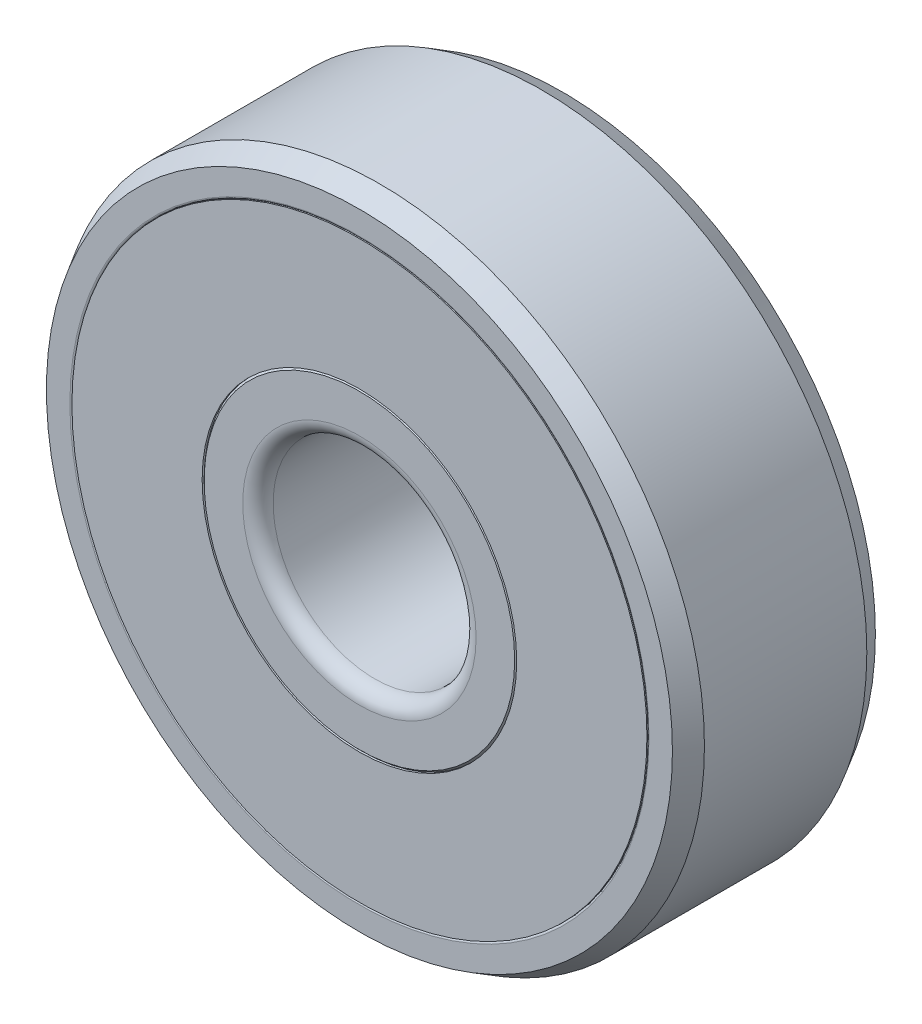
SolidWorks part; units mm, degrees
ref_plane "Front Plane" through (0, 0, 0) normal (0, 0, 1) x (1, 0, 0)
ref_plane "Top Plane" through (0, 0, 0) normal (0, 1, 0) x (1, 0, 0)
ref_plane "Right Plane" through (0, 0, 0) normal (1, 0, 0) x (0, 0, -1)
sketch "Sketch1" plane through (0, 0, 0) normal (0, 0, 1) x (1, 0, 0)
  line L0 (0, 5.25) -> (0, 8) construction
  line L1 (0, 2.5) -> (0, 5.25) construction
  line L2 (0, 8) -> (0, 7.0833) construction
  line L3 (0, 7.0833) -> (0, 6.1667) construction
  line L4 (0, 6.1667) -> (0, 5.25) construction
  circle A0 centre (0, 0) radius 2.5
  circle A1 centre (0, 0) radius 8
  circle A2 centre (0, 0) radius 7.0833 construction
  circle A4 centre (0, 0) radius 3.875 construction
  point P6 (0, 3.875)
  dimension "OD" = 16
  dimension "ID" = 5
sketch "Sketch2" plane through (0, 0, 0) normal (1, 0, 0) x (0, 0, -1)
  line L0 (-2.5, 8) -> (2.5, 8) construction
  line L1 (2.5, 8) -> (2.5, -8) construction
  line L2 (2.5, 0) -> (-2.5, 0) construction
  line L3 (-2.5, 2.5) -> (-2.5, -2.5) construction
  point P2 (0, 8)
  dimension "Width" = 5
  dimension "For Shaft Diameter" = 5
  dimension "For Housing ID" = 16
sketch "Sketch3" plane through (0, 0, 0) normal (1, 0, 0) x (0, 0, -1)
  line L0 (-2, -8) -> (2, -8)
  line L3 (-2.5, -7.1333) -> (-2.5, -7.7113)
  line L4 (0, -3.875) -> (0, -7.0833) construction
  line L5 (-2, -8) -> (-2.5, -7.7113)
  line L6 (-2.125, -2.5) -> (2.125, -2.5)
  line L7 (-1.5278, -7.0833) -> (-1.5278, -7.3889) construction
  line L8 (-2.45, -3.875) -> (-1.5278, -3.875)
  line L9 (-2.5, -3.875) -> (0, -3.875) construction
  line L11 (-2.5, -7.0833) -> (-2.5, -3.875) construction
  line L12 (-2.5, -3.825) -> (-2.5, -2.875)
  line L14 (-2.5, 0) -> (2.5, 0) construction
  line L15 (-2.45, -7.0833) -> (-1.5278, -7.0833)
  line L17 (0, 0) -> (0, -8) construction
  line L18 (-1.5278, -7.3889) -> (-1.5278, -7.6944) construction
  line L19 (2, -8) -> (2.5, -7.7113)
  line L20 (0, -7.0833) -> (-2.5, -7.0833) construction
  line L21 (-2.5, 2.5) -> (-2.5, -2.5) construction
  line L22 (-1.5278, -7.6944) -> (-1.5278, -8) construction
  line L30 (-2.5, -3.825) -> (-2.45, -3.875)
  line L31 (2.45, -3.875) -> (1.5278, -3.875)
  line L32 (2.5, -3.825) -> (2.45, -3.875)
  line L33 (2.5, -3.825) -> (2.5, -2.875)
  line L34 (2.45, -7.0833) -> (1.5278, -7.0833)
  line L35 (2.5, -7.1333) -> (2.5, -7.7113)
  line L36 (0, 8) -> (0, -8) construction
  arc A0 (0, -3.2639) -> (0, -7.6944) centre (0, -5.4792) ccw construction
  arc A1 (-1.5278, -3.875) -> (1.5278, -3.875) centre (0, -5.4792) cw
  arc A2 (-1.5278, -7.0833) -> (1.5278, -7.0833) centre (0, -5.4792) ccw
  arc A4 (-2.45, -7.0833) -> (-2.5, -7.1333) centre (-2.45, -7.1333) ccw
  arc A5 (-2.125, -2.5) -> (-2.5, -2.875) centre (-2.125, -2.875) ccw
  arc A6 (2.125, -2.5) -> (2.5, -2.875) centre (2.125, -2.875) cw
  arc A7 (2.45, -7.0833) -> (2.5, -7.1333) centre (2.45, -7.1333) cw
  point P28 (0, -5.4792)
  point P46 (-2.5, -2.5)
  point P54 (0, -2.5)
  dimension "D4" = 0.05
  dimension "D7" = 0.375
  dimension "D5" = 45
  dimension "D6" = 0.05
  dimension "D3" = 0.5
  dimension "D2" = 60
revolve "Revolve1" add sketch "Sketch3" angle 360 about L14
sketch "Sketch4" plane through (0, 0, 0) normal (1, 0, 0) x (0, 0, -1)
  line L0 (-2.45, -7.0833) -> (-1.5278, -7.0833) construction
  line L1 (-2.5, -3.875) -> (-2.2865, -3.875)
  line L2 (-2.5, -3.875) -> (-2.5, -7.0833)
  line L3 (-2.5, -7.0833) -> (-2.2865, -7.0833)
  line L4 (-2.2865, -3.875) -> (-2.2865, -7.0833)
  line L5 (-2.5, -3.825) -> (-2.5, -2.875) construction
  line L6 (-2.5, -5.4792) -> (-2.4288, -5.4792) construction
  line L7 (-2.4288, -5.4792) -> (-2.3576, -5.4792) construction
  line L8 (-2.3576, -5.4792) -> (-2.2865, -5.4792) construction
  line L9 (-2.2865, -5.4792) -> (-2.2153, -5.4792) construction
  line L10 (-2.5, -7.0833) -> (-2.5, -3.875) construction
  line L11 (-2.45, -3.875) -> (-1.5278, -3.875) construction
  arc A1 (0, -3.2639) -> (0, -7.6944) centre (0, -5.4792) ccw construction
revolve "Revolve2" add sketch "Sketch4" angle 360 about L14
sketch "Sketch5" plane through (0, 0, 0) normal (1, 0, 0) x (0, 0, -1)
  line L2 (0, -3.2639) -> (0, -7.6944)
  arc A2 (0, -7.6944) -> (0, -3.2639) centre (0, -5.4792) cw
revolve "Revolve3" add sketch "Sketch5" angle 360 about L17
pattern_circular "CirPattern1" count 7 over 360 about axis through (0, 0, 2.5) along (0, 0, -1) of bodies 138
ref_axis "Bearing Axis" through (0, 0, -13.2133) along (0, 0, 1)
equation "\"D4@Sketch3\"=\"Width@Sketch2\"*.01"
equation "\"D6@Sketch3\"=\"Width@Sketch2\"*.01"
equation "\"D7@Sketch3\"=\"Width@Sketch2\"*.075"
equation "\"D3@Sketch3\"=\"Width@Sketch2\"*.1"
